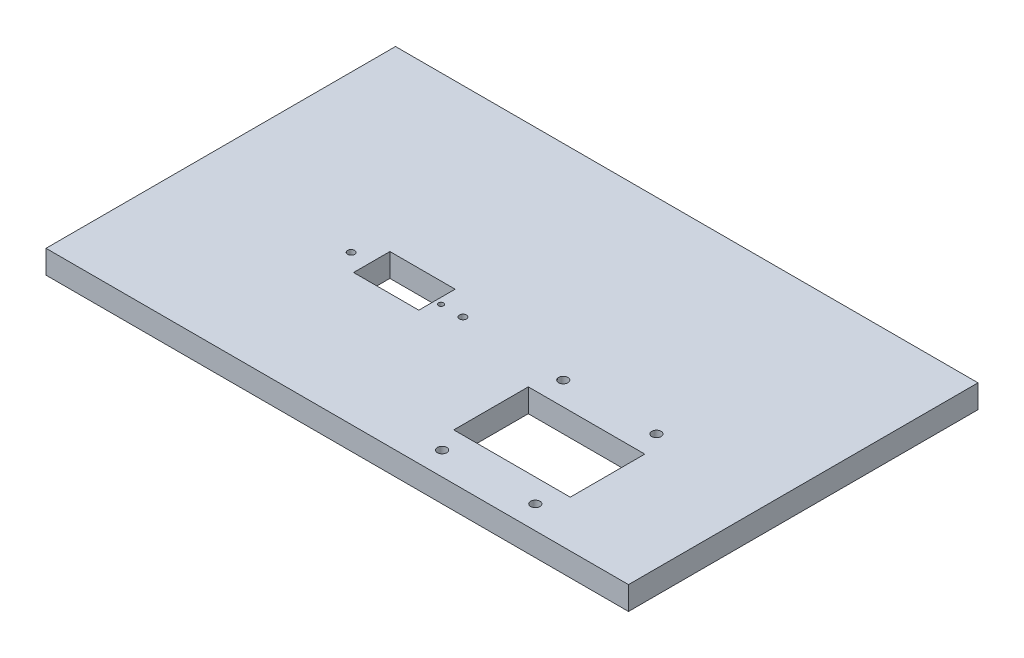
SolidWorks part; units mm, degrees
ref_plane "Front Plane" through (0, 0, 0) normal (0, 0, 1) x (1, 0, 0)
ref_plane "Top Plane" through (0, 0, 0) normal (0, 1, 0) x (1, 0, 0)
ref_plane "Right Plane" through (0, 0, 0) normal (1, 0, 0) x (0, 0, -1)
sketch "Sketch2" plane through (0, 0, 0) normal (0, 1, 0) x (1, 0, 0)
  line L1 (-125, 75) -> (125, 75)
  line L2 (-125, 75) -> (-125, -75)
  line L3 (-125, -75) -> (125, -75)
  line L4 (125, 75) -> (125, -75)
  line L5 (-125, 75) -> (125, -75) construction
  line L6 (-125, -75) -> (125, 75) construction
  point P0 (0, 0)
  dimension "D1" = 250
  dimension "D2" = 150
extrude "Boss-Extrude1" add sketch "Sketch2" along normal blind 10
sketch "Sketch3" plane through (0, 10, 0) normal (0, 1, 0) x (1, 0, 0)
  line L1 (30, -23) -> (80, -23)
  line L2 (30, -23) -> (30, -55)
  line L3 (30, -55) -> (80, -55)
  line L4 (80, -23) -> (80, -55)
  circle A0 centre (35, -13) radius 2
  circle A1 centre (75, -13) radius 2
  circle A2 centre (35, -65) radius 2
  circle A3 centre (75, -65) radius 2
extrude "Cut-Extrude1" cut sketch "Sketch3" against normal blind 10
sketch "Sketch4" plane through (0, 10, 0) normal (0, 1, 0) x (1, 0, 0)
  line L1 (-50, -2.4028) -> (-22, -2.4028)
  line L2 (-50, -2.4028) -> (-50, -18)
  line L3 (-50, -18) -> (-22, -18)
  line L4 (-22, -2.4028) -> (-22, -18)
  dimension "D1" = 28
extrude "Cut-Extrude2" cut sketch "Sketch4" against normal blind 10
sketch "Sketch6" plane through (0, 10, 0) normal (0, 1, 0) x (1, 0, 0)
  circle A0 centre (-19.4, -11.05) radius 1.1
  circle A1 centre (-47.1, -11.05) radius 1.1
extrude "Cut-Extrude3" cut sketch "Sketch6" against normal blind 10
sketch "Sketch7" plane through (0, 10, 0) normal (0, 1, 0) x (1, 0, 0)
  circle A0 centre (-10, -11.05) radius 1.5
  circle A1 centre (-58, -11.05) radius 1.5
extrude "Cut-Extrude4" cut sketch "Sketch7" against normal blind 10
